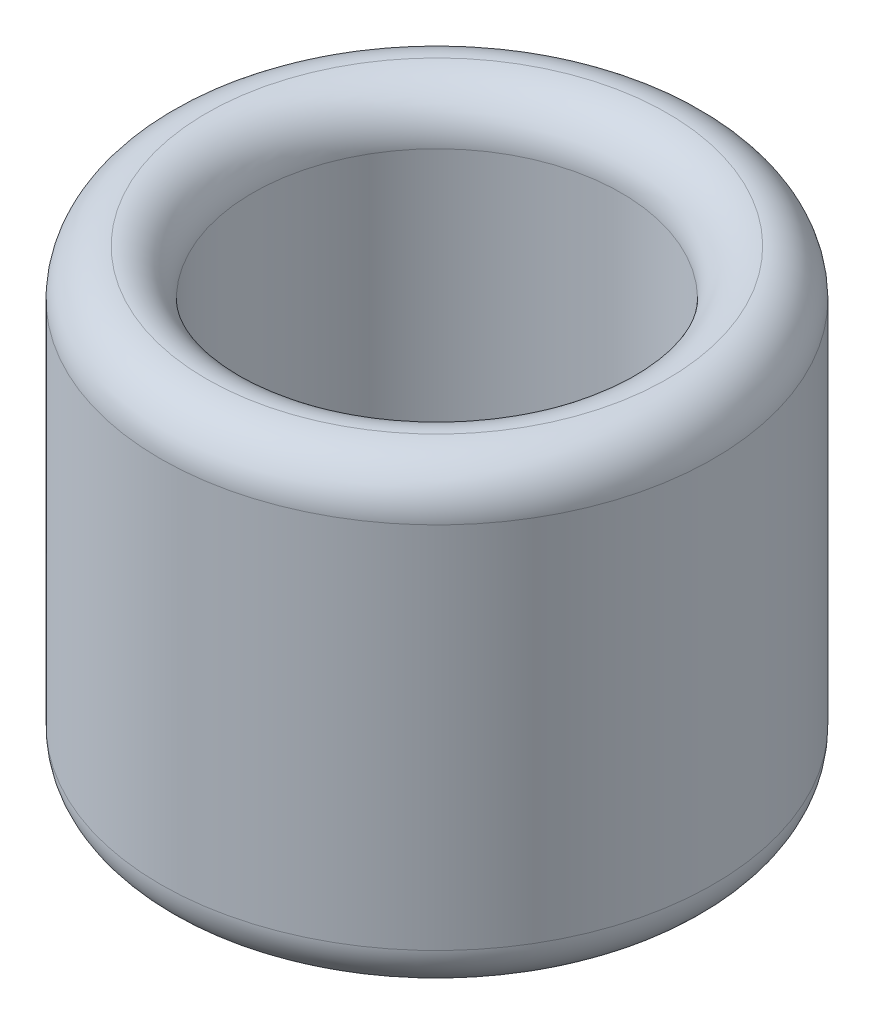
SolidWorks part; units mm, degrees
material "1060 Сплав"
ref_plane "Спереди" through (0, 0, 0) normal (0, 0, 1) x (1, 0, 0)
ref_plane "Сверху" through (0, 0, 0) normal (0, 1, 0) x (1, 0, 0)
ref_plane "Справа" through (0, 0, 0) normal (1, 0, 0) x (0, 0, -1)
other "Configuration Table"
sketch "Эскиз1" plane through (0, 0, 0) normal (0, 1, 0) x (1, 0, 0)
  circle A0 centre (0, 0) radius 6
  circle A1 centre (0, 0) radius 4
  dimension "D1" = 12
  dimension "D2" = 8
extrude "Бобышка-Вытянуть1" add sketch "Эскиз1" along normal blind 10
fillet "圆角1" radius 1 4 edges at (0, 10, 4) (0, 10, 6) (0, 0, 4) (0, 0, 6)
